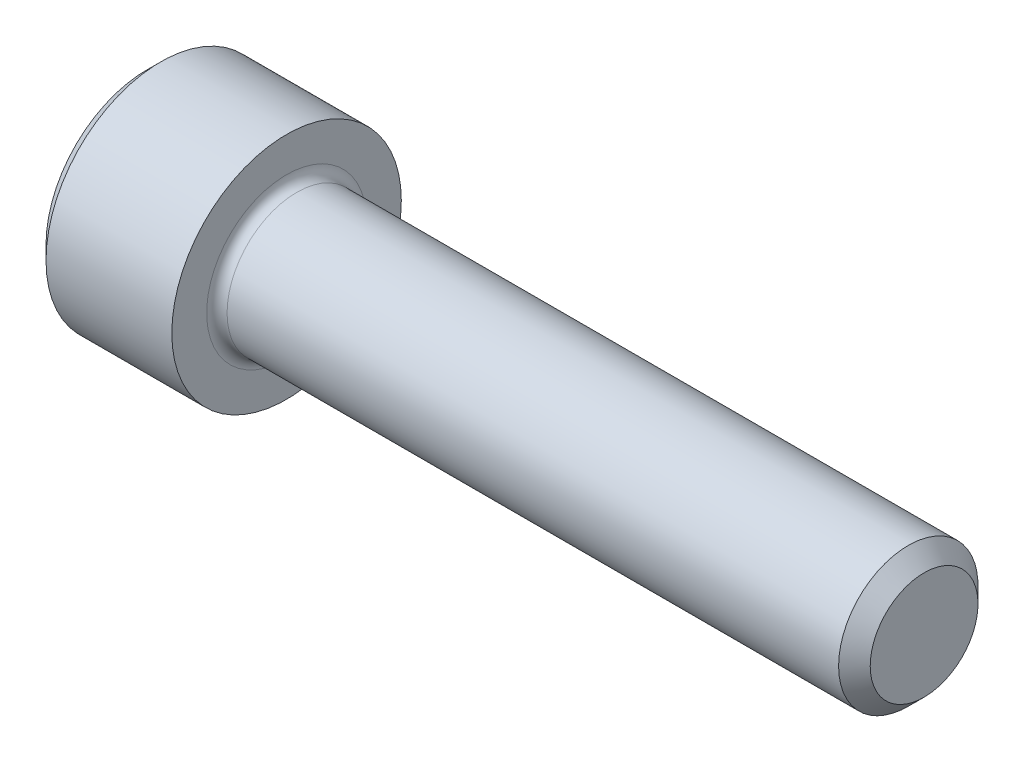
SolidWorks part; units mm, degrees
note: '?' marks a value the reader was unsure of.
revolve "Base-Revolve" add sketch "BodySke"
sketch "BodySke" plane through (0, 0, 0) normal (0, 0, 1) x (1, 0, 0)
  line L0 (0, 0) -> (0, 3.0226)
  line L1 (0.4064, 3.429) -> (4.1656, 3.429)
  line L2 (4.1656, 3.429) -> (4.1656, 2.0828)
  line L3 (4.1656, 2.0828) -> (22.7432, 2.0828)
  line L4 (23.2156, 1.6104) -> (23.2156, 0)
  line L5 (23.2156, 0) -> (0, 0)
  line L6 (-31.75, 0) -> (127, 0) construction
  line L7 (0, 3.0226) -> (0.4064, 3.429)
  line L8 (23.2156, 1.6104) -> (22.7432, 2.0828)
  line L9 (0, -3.0226) -> (0.4064, -3.429) construction
  line L10 (23.2156, -1.6104) -> (22.7432, -2.0828) construction
  line L11 (4.9581, 9.525) -> (4.9581, 3.175) construction
  line L12 (7.3406, 9.525) -> (7.3406, 3.175) construction
  line L13 (-14.8844, 9.525) -> (-14.8844, 3.175) construction
  dimension "Diameter" = 4.1656
  dimension "Head_ht" = 4.1656
  dimension "Length" = 19.05
  dimension "Body_ch_ang" = 45
  dimension "Head_dia" = 6.858
  dimension "Head_ch_ang" = 45
  dimension "Head_side_ht" = 3.7592
  dimension "Minor_dia" = 3.2207
  dimension "Advance" = 0.7925
  dimension "Thread_nom" = 15.875
  dimension "Thread_length" = 38.1
cosmetic thread "ThreadCosmetic" [suppressed]
fillet "Fillet1" radius 0.3048 1 edges at (4.1656, 0, 2.0828)
ref_plane "Plane1" through (0, 0, 0) normal (0, 0, 1) x (1, 0, 0)
ref_plane "Plane2" through (0, 0, 0) normal (0, 1, 0) x (1, 0, 0)
ref_plane "Plane3" through (0, 0, 0) normal (1, 0, 0) x (0, 0, -1)
sketch "Sketch2" plane through (0, 0, 0) normal (0, 0, 1) x (1, 0, 0)
  line L0 (0, 1.778) -> (1.9558, 1.778)
  line L1 (1.9558, 1.778) -> (2.9823, 0)
  line L2 (-31.75, 0) -> (127, 0) construction
  line L3 (2.9823, 0) -> (0, 0)
  line L4 (0, 0) -> (0, 1.778)
  line L5 (0, 3.0226) -> (0, -3.0226) construction
  line L6 (0, 0) -> (47.625, 0) construction
  line L7 (4.1656, -3.429) -> (4.1656, 3.429) construction
  dimension "D1" = 1.778
  dimension "D2" = 60
revolve "Hex-PreBroach" [suppressed] cut sketch "Sketch2" angle 360 about L6
sketch "Sketch3" plane through (0, 0, 0) normal (-1, 0, 0) x (0, 0.5, 0.866)
  line L0 (1.0265, 1.778) -> (-1.0265, 1.778)
  line L1 (-1.0265, 1.778) -> (-2.0531, 0)
  line L2 (1.0265, 1.778) -> (2.0531, 0)
  line L3 (1.0265, -1.778) -> (2.0531, 0)
  line L4 (1.0265, -1.778) -> (-1.0265, -1.778)
  line L5 (-1.0265, -1.778) -> (-2.0531, 0)
  dimension "D1" = 1.778
  dimension "D2" = 1.778
extrude "Hex" cut sketch "Sketch3" against normal blind 1.9558
sketch "Sketch4" plane through (0, 0, 0) normal (-1, 0, 0) x (0, 0, 1)
  line L0 (0, 0) -> (2.1971, 0)
  line L1 (0, 0) -> (6.1484, 3.5498) construction
  line L2 (0, 0) -> (1.0985, 1.9027)
  line L3 (1.8302, 0.5287) -> (2.0897, 0.6786)
  line L4 (1.373, 1.3206) -> (1.6325, 1.4704)
  arc A0 (1.8302, 0.5287) -> (1.373, 1.3206) centre (0, 0) ccw
  arc A1 (2.1971, 0) -> (2.0897, 0.6786) centre (0, 0) ccw
  arc A2 (1.0985, 1.9027) -> (1.6325, 1.4704) centre (0, 0) cw
  dimension "D1" = 30
  dimension "D2" = 60
  dimension "Spline_p_dim" = 0.9144
  dimension "D3" = 0.4572
extrude "Spline" [suppressed] cut sketch "Sketch4" against normal blind 1.9558
pattern_circular "CirPattern1" [suppressed] count 0 every? 60?
sketch "Sketch5" plane through (0, 0, 0) normal (0, 0, 1) x (1, 0, 0)
  line L0 (-31.75, 0) -> (127, 0) construction
  line L2 (0, 3.0226) -> (0, -3.0226) construction
  circle A0 centre (1.524, 0) radius 0.5905
  dimension "Drilled_hole_dia" = 1.1811
  dimension "Drilled_hole_loc" = 1.524
extrude "Hole" [suppressed] cut sketch "Sketch5" against normal through all and the other way through all
pattern_circular "Drilled-4" [suppressed] count 2 every 60
pattern_circular "Drilled-6" [suppressed] count 3 every 60
sketch "ThdSchSke" plane through (0, 0, 0) normal (0, 0, 1) x (1, 0, 0)
  line L0 (63.5, -1.6104) -> (63.1692, -2.0828)
  line L1 (63.5, -1.6104) -> (63.8308, -2.0828)
  line L2 (63.8308, -2.0828) -> (63.8308, -2.6035)
  line L3 (-3.175, 0) -> (5.1513, 0) construction
  line L5 (63.8308, -2.6035) -> (63.1692, -2.6035)
  line L6 (63.1692, -2.6035) -> (63.1692, -2.0828)
  line L7 (0, 3.0226) -> (0, -3.0226) construction
  dimension "Thread_minor" = 3.2207
  dimension "Diameter" = 4.1656
  dimension "Start" = 63.5
revolve "ThreadSchematic" [suppressed] cut sketch "ThdSchSke" angle 360 about L3
pattern_linear "ThdSchPat" [suppressed]
equation "\"D2@Sketch3\" = \"Hex_size@Sketch3\" / 2"
equation "\"D1@Sketch3\" = \"Hex_size@Sketch3\" / 2"
equation "\"D1@Sketch2\" = \"Hex_size@Sketch3\" / 2"
equation "\"D3@Sketch4\" = \"Spline_p_dim@Sketch4\" / 2"
equation "\"Thread_minor@ThreadCosmetic\"  =  \"Minor_dia@BodySke\""
equation "\"D2@CirPattern1\" = 360 / \"Num_teeth@CirPattern1\""
equation "\"Wall_thickness@Sketch2\" = \"Head_ht@BodySke\" - \"Key_eng@Hex\""
equation "\"Thread_length@ThreadCosmetic\" = ((sgn( (\"Length@BodySke\" - \"Advance@BodySke\" ) - \"Thread_nom@BodySke\" )-1)*( (\"Length@BodySke\" - \"Advance@BodySke\" ) - \"Thread_nom@BodySke\" ))/-2+ \"Thread_nom@BodySke\""
equation "\"Thread_minor@ThdSchSke\" = \"Minor_dia@BodySke\""
equation "\"Diameter@ThdSchSke\" = \"Diameter@BodySke\""
equation "\"Overcut@ThdSchSke\" = \"Diameter@BodySke\" * 1.25"
equation "\"Start@ThdSchSke\" = \"Head_ht@BodySke\" + \"Length@BodySke\" - \"Thread_length@ThreadCosmetic\"  '---Non-countersunk---"
equation "\"Num_threads@ThdSchPat\" = int( \"Thread_length@ThreadCosmetic\" / \"Advance@BodySke\" + 0.999 )  + 1"
equation "\"Advance@ThdSchPat\" = \"Thread_length@ThreadCosmetic\" /  (\"Num_threads@ThdSchPat\" - 1) 'relax it"
equation "\"Num_threads@ThdSchPat\" = \"Num_threads@ThdSchPat\" - sgn( \"Num_threads@ThdSchPat\" - 1) '---chamfered tips only---"
